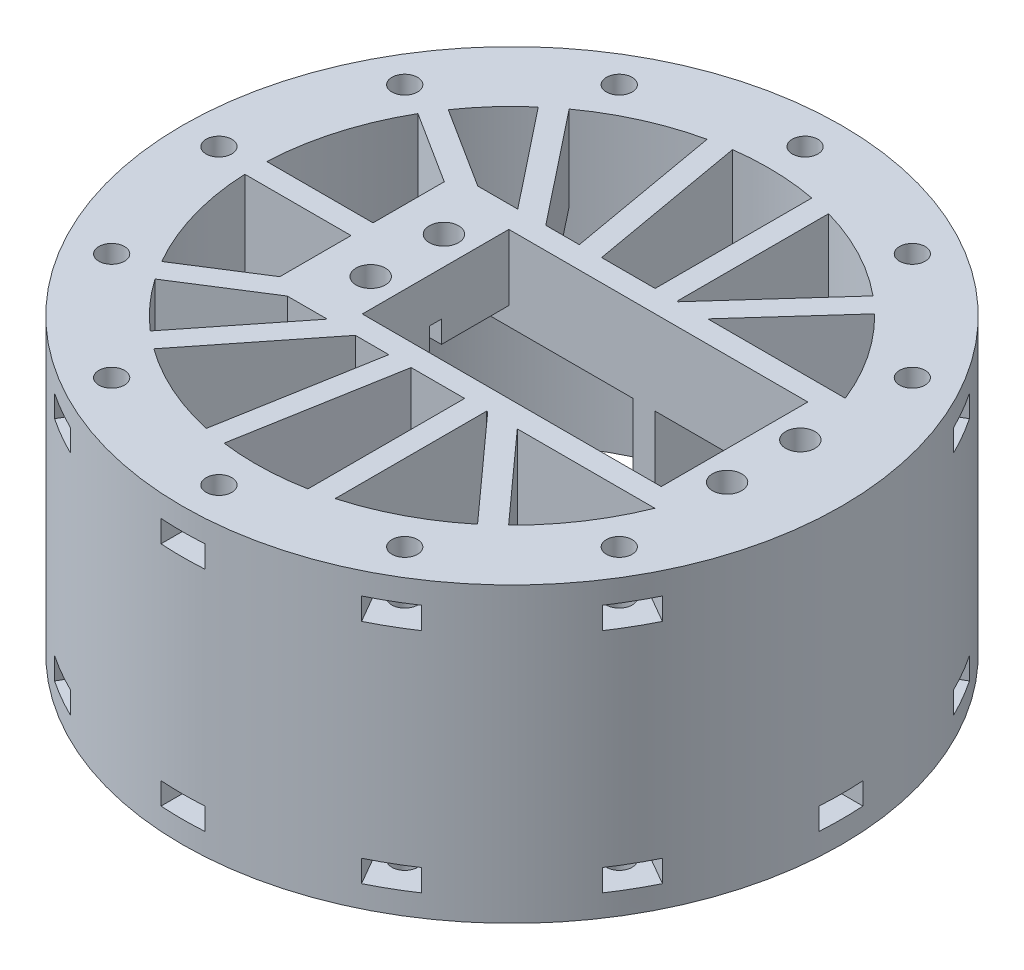
SolidWorks part; units mm, degrees
ref_plane "Front Plane" through (0, 0, 0) normal (0, 0, 1) x (1, 0, 0)
ref_plane "Top Plane" through (0, 0, 0) normal (0, 1, 0) x (1, 0, 0)
ref_plane "Right Plane" through (0, 0, 0) normal (1, 0, 0) x (0, 0, -1)
sketch "Sketch1" plane through (0, 0, 0) normal (0, 1, 0) x (1, 0, 0)
  line L0 (-43.0464, 0) -> (41.9462, 0) construction
  line L1 (0, 43.1152) -> (0, -41.8775) construction
  circle A1 centre (0, 0) radius 45
  dimension "D2" = 90
extrude "Boss-Extrude1" add sketch "Sketch1" along normal blind 40
sketch "Sketch2" plane through (0, 0, 0) normal (0, -1, 0) x (1, 0, 0)
  circle A0 centre (0, 0) radius 35
  dimension "D1" = 70
extrude "Cut-Extrude1" cut sketch "Sketch2" against normal blind 28.5
sketch "Sketch3" plane through (0, 28.5, 0) normal (0, -1, 0) x (1, 0, 0)
  line L0 (35, 0) -> (-35, 0) construction
  line L1 (0, -35) -> (0, 35) construction
  line L3 (37.5324, -10) -> (-17.4676, -10)
  line L4 (37.5324, -10) -> (37.5324, 10)
  line L5 (37.5324, 10) -> (-17.4676, 10)
  line L6 (-17.4676, -10) -> (-17.4676, 10)
  circle A0 centre (0, 0) radius 35 construction
  circle A1 centre (0, 0) radius 35 construction
  dimension "D1" = 20
  dimension "D2" = 55
  dimension "D3" = 10
  dimension "D4" = 37.5324
extrude "Cut-Extrude2" cut sketch "Sketch3" against normal blind 2.5 and the other way up to next
sketch "Sketch4" plane through (0, 31, 0) normal (0, -1, 0) x (1, 0, 0)
  line L0 (37.5324, 0) -> (-17.4676, 0) construction
  line L1 (37.5324, 10) -> (37.5324, -10) construction
  line L2 (-17.4676, 10) -> (-17.4676, -10) construction
  line L3 (0, -10) -> (0, 10) construction
  line L4 (-17.4676, -10) -> (33.541, -10) construction
  line L5 (33.541, 10) -> (-17.4676, 10) construction
  line L7 (30.3722, -10) -> (-10.4278, -10)
  line L8 (30.3722, -10) -> (30.3722, 10)
  line L9 (30.3722, 10) -> (-10.4278, 10)
  line L10 (-10.4278, -10) -> (-10.4278, 10)
  dimension "D1" = 20
  dimension "D2" = 40.8
  dimension "D3" = 30.3722
  dimension "D4" = 10
extrude "Cut-Extrude3" cut sketch "Sketch4" against normal blind 9
sketch "Sketch8" plane through (0, 28.5, 0) normal (0, -1, 0) x (1, 0, 0)
  line L0 (-17.4676, 0) -> (-35, 0) construction
  line L1 (-17.4676, 10) -> (-17.4676, -10) construction
  line L2 (8.0367, 10) -> (8.0367, 34.0648) construction
  line L3 (33.541, 10) -> (-17.4676, 10) construction
  line L4 (8.0367, -10) -> (8.0367, -29.3194) construction
  line L5 (-17.4676, -10) -> (33.541, -10) construction
  line L6 (6.5367, 10) -> (6.5367, 34.3842)
  line L7 (9.5367, 10) -> (9.5367, 33.6757)
  line L8 (9.5367, 10) -> (6.5367, 10)
  line L9 (9.5367, -10) -> (6.5367, -10)
  line L10 (6.5367, -10) -> (6.5367, -34.3842)
  line L11 (9.5367, -10) -> (9.5367, -33.6757)
  line L12 (-17.4676, 1.5) -> (-34.9678, 1.5)
  line L13 (-17.4676, -1.5) -> (-34.9678, -1.5)
  line L14 (-17.4676, 1.5) -> (-17.4676, -1.5)
  arc A0 (33.541, 10) -> (33.541, -10) centre (0, 0) ccw construction
  arc A1 (9.5367, 33.6757) -> (6.5367, 34.3842) centre (7.9531, 33.6757) ccw
  arc A2 (9.5367, -33.6757) -> (6.5367, -34.3842) centre (7.9531, -33.6757) cw
  arc A3 (-34.9678, 1.5) -> (-34.9678, -1.5) centre (-34.9678, 0) ccw
  dimension "D3" = 1.5
  dimension "D1" = 1.5
  dimension "D2" = 1.5
  dimension "D4" = 1.5
extrude "Boss-Extrude2" add sketch "Sketch8" along normal through all
sketch "Sketch16" plane through (0, 31, 0) normal (0, -1, 0) x (1, 0, 0)
  line L0 (-17.4676, 0) -> (37.5324, 0) construction
  line L1 (-17.4676, 10) -> (-17.4676, -10) construction
  line L2 (37.5324, -10) -> (37.5324, 10) construction
  line L3 (30.3722, -0.8) -> (37.5324, -0.8)
  line L4 (-10.4278, -0.8) -> (-17.4676, -0.8)
  line L5 (-10.4278, 10) -> (-10.4278, -10) construction
  line L6 (-10.4278, 0.8) -> (-17.4676, 0.8)
  line L7 (-17.4676, 0.8) -> (-17.4676, -0.8)
  line L8 (-10.4278, 0.8) -> (-10.4278, -0.8)
  line L9 (30.3722, -10) -> (30.3722, 10) construction
  line L10 (30.3722, 0.8) -> (37.5324, 0.8)
  line L11 (37.5324, 0.8) -> (37.5324, -0.8)
  line L12 (30.3722, 0.8) -> (30.3722, -0.8)
  dimension "D1" = 0.8
extrude "Cut-Extrude10" cut sketch "Sketch16" against normal blind 3
sketch "Sketch27" plane through (0, 0, 0) normal (0, -1, 0) x (1, 0, 0)
  line L0 (0, 0) -> (0, -53.17) construction
  line L1 (0, 0) -> (47.7582, -27.5732) construction
  line L3 (31.641, -18.2679) -> (31.641, -21.7321) construction
  line L4 (31.641, -21.7321) -> (34.641, -23.4641) construction
  line L5 (34.641, -23.4641) -> (37.641, -21.7321) construction
  line L6 (37.641, -21.7321) -> (37.641, -18.2679) construction
  line L7 (37.641, -18.2679) -> (34.641, -16.5359) construction
  line L8 (34.641, -16.5359) -> (31.641, -18.2679) construction
  circle A0 centre (0, 0) radius 40 construction
  circle A1 centre (34.641, -20) radius 1.75
  circle A2 centre (0, 0) radius 35 construction
  circle A3 centre (34.641, -20) radius 3 construction
  circle A4 centre (20, -34.641) radius 1.75
  circle A5 centre (0, -40) radius 1.75
  circle A6 centre (-20, -34.641) radius 1.75
  circle A7 centre (-34.641, -20) radius 1.75
  circle A8 centre (-40, 0) radius 1.75
  circle A9 centre (-34.641, 20) radius 1.75
  circle A10 centre (-20, 34.641) radius 1.75
  circle A11 centre (0, 40) radius 1.75
  circle A12 centre (20, 34.641) radius 1.75
  circle A13 centre (34.641, 20) radius 1.75
  circle A15 centre (40, 0) radius 1.75 [skipped]
  point P28 (0, 0)
  point P41 (0, 0)
  dimension "D1" = 80
  dimension "D3" = 3.5
  dimension "D4" = 70
  dimension "D5" = 6
  dimension "D6" = 12
  dimension "D2" = 60
extrude "Cut-Extrude15" cut sketch "Sketch27" against normal through all
ref_plane "Plane1" through (0, 37, 0) normal (0, 1, 0) x (1, 0, 0)
sketch "Sketch28" plane through (0, 37, 0) normal (0, 1, 0) x (1, 0, 0)
  line L0 (0, 0) -> (-54.493, 0) construction
  line L1 (-31.641, 18.2679) -> (-31.641, 21.7321)
  line L2 (-36.5359, 0) -> (-38.2679, 3)
  line L3 (-38.2679, 3) -> (-44.8999, 3)
  line L4 (-31.641, 21.7321) -> (-37.3844, 25.048)
  line L5 (-40.3844, 19.8519) -> (-34.641, 16.5359)
  line L6 (-44.8999, -3) -> (-38.2679, -3)
  line L7 (-38.2679, -3) -> (-36.5359, 0)
  line L8 (-43.4641, 0) -> (-42.5981, -1.5) [skipped]
  line L9 (-41.7321, 3) -> (-42.5981, 1.5) [skipped]
  line L10 (-34.641, 16.5359) -> (-31.641, 18.2679)
  line L11 (-18.2679, 31.641) -> (-16.5359, 34.641)
  line L12 (-16.5359, 34.641) -> (-19.8519, 40.3844)
  line L13 (-25.048, 37.3844) -> (-21.7321, 31.641)
  line L14 (-21.7321, 31.641) -> (-18.2679, 31.641)
  line L15 (0, 36.5359) -> (3, 38.2679)
  line L16 (3, 38.2679) -> (3, 44.8999)
  line L17 (-3, 44.8999) -> (-3, 38.2679)
  line L18 (-3, 38.2679) -> (0, 36.5359)
  line L19 (18.2679, 31.641) -> (21.7321, 31.641)
  line L20 (21.7321, 31.641) -> (25.048, 37.3844)
  line L21 (19.8519, 40.3844) -> (16.5359, 34.641)
  line L22 (16.5359, 34.641) -> (18.2679, 31.641)
  line L23 (31.641, 18.2679) -> (34.641, 16.5359)
  line L24 (34.641, 16.5359) -> (40.3844, 19.8519)
  line L25 (37.3844, 25.048) -> (31.641, 21.7321)
  line L26 (31.641, 21.7321) -> (31.641, 18.2679)
  line L31 (31.641, -18.2679) -> (31.641, -21.7321)
  line L32 (31.641, -21.7321) -> (37.3844, -25.048)
  line L33 (40.3844, -19.8519) -> (34.641, -16.5359)
  line L34 (34.641, -16.5359) -> (31.641, -18.2679)
  line L35 (18.2679, -31.641) -> (16.5359, -34.641)
  line L36 (16.5359, -34.641) -> (19.8519, -40.3844)
  line L37 (25.048, -37.3844) -> (21.7321, -31.641)
  line L38 (21.7321, -31.641) -> (18.2679, -31.641)
  line L39 (0, -36.5359) -> (-3, -38.2679)
  line L40 (-3, -38.2679) -> (-3, -44.8999)
  line L41 (3, -44.8999) -> (3, -38.2679)
  line L42 (3, -38.2679) -> (0, -36.5359)
  line L43 (-18.2679, -31.641) -> (-21.7321, -31.641)
  line L44 (-21.7321, -31.641) -> (-25.048, -37.3844)
  line L45 (-19.8519, -40.3844) -> (-16.5359, -34.641)
  line L46 (-16.5359, -34.641) -> (-18.2679, -31.641)
  line L47 (-31.641, -18.2679) -> (-34.641, -16.5359)
  line L48 (-34.641, -16.5359) -> (-40.3844, -19.8519)
  line L49 (-37.3844, -25.048) -> (-31.641, -21.7321)
  line L50 (-31.641, -21.7321) -> (-31.641, -18.2679)
  line L51 (36.5359, 0) -> (38.2679, -3) [skipped]
  line L52 (38.2679, -3) -> (44.8999, -3) [skipped]
  line L53 (44.8999, 3) -> (38.2679, 3) [skipped]
  line L54 (38.2679, 3) -> (36.5359, 0) [skipped]
  arc A0 (-44.8999, 3) -> (-44.8999, -3) centre (0, 0) ccw
  circle A1 centre (-40, 0) radius 3 construction
  arc A2 (-37.3844, 25.048) -> (-40.3844, 19.8519) centre (0, 0) ccw
  circle A3 centre (-34.641, 20) radius 3 construction
  arc A4 (-19.8519, 40.3844) -> (-25.048, 37.3844) centre (0, 0) ccw
  circle A5 centre (-20, 34.641) radius 3 construction
  arc A6 (3, 44.8999) -> (-3, 44.8999) centre (0, 0) ccw
  circle A7 centre (0, 40) radius 3 construction
  arc A8 (25.048, 37.3844) -> (19.8519, 40.3844) centre (0, 0) ccw
  circle A9 centre (20, 34.641) radius 3 construction
  arc A10 (40.3844, 19.8519) -> (37.3844, 25.048) centre (0, 0) ccw
  circle A11 centre (34.641, 20) radius 3 construction
  arc A14 (37.3844, -25.048) -> (40.3844, -19.8519) centre (0, 0) ccw
  circle A15 centre (34.641, -20) radius 3 construction
  arc A16 (19.8519, -40.3844) -> (25.048, -37.3844) centre (0, 0) ccw
  circle A17 centre (20, -34.641) radius 3 construction
  arc A18 (-3, -44.8999) -> (3, -44.8999) centre (0, 0) ccw
  circle A19 centre (0, -40) radius 3 construction
  arc A20 (-25.048, -37.3844) -> (-19.8519, -40.3844) centre (0, 0) ccw
  circle A21 centre (-20, -34.641) radius 3 construction
  arc A22 (-40.3844, -19.8519) -> (-37.3844, -25.048) centre (0, 0) ccw
  circle A23 centre (-34.641, -20) radius 3 construction
  arc A24 (44.8999, -3) -> (44.8999, 3) centre (0, 0) ccw [skipped]
  circle A25 centre (40, 0) radius 3 construction
  point P94 (0, 0)
  dimension "D1" = 90
  dimension "D2" = 6
  dimension "D3" = 12
extrude "Cut-Extrude17" cut sketch "Sketch28" against normal blind 3
sketch "Sketch29" plane through (0, 28.5, 0) normal (0, -1, 0) x (1, 0, 0)
  line L0 (32.4962, -13) -> (13.7255, -13)
  line L1 (9.5367, -33.6757) -> (9.5367, -10) construction
  line L2 (9.5367, -13) -> (9.5367, -33.6757)
  line L3 (9.5367, -10) -> (33.541, -10) construction
  line L4 (6.5367, -13) -> (-0.7691, -13)
  line L5 (6.5367, -10) -> (6.5367, -34.3842) construction
  line L6 (-20.4676, -11.223) -> (-20.4676, -1.5)
  line L7 (-34.9678, -1.5) -> (-17.4676, -1.5) construction
  line L8 (-20.4676, -1.5) -> (-34.9678, -1.5)
  line L9 (-17.4676, -0.8) -> (-17.4676, -10) construction
  line L10 (32.4962, 13) -> (13.7255, 13)
  line L11 (9.5367, 10) -> (9.5367, 33.6757) construction
  line L12 (9.5367, 13) -> (9.5367, 33.6757)
  line L13 (-7.5493, 34.1761) -> (-3.8154, 13)
  line L14 (6.5367, 13) -> (-0.7691, 13)
  line L15 (6.5367, 34.3842) -> (6.5367, 10) construction
  line L16 (-20.4676, 11.223) -> (-20.4676, 1.5)
  line L17 (-17.4676, 1.5) -> (-34.9678, 1.5) construction
  line L18 (-20.4676, 1.5) -> (-34.9678, 1.5)
  line L19 (6.5367, 13) -> (6.5367, 34.3842)
  line L20 (6.5367, -34.3842) -> (6.5367, -13)
  line L21 (0, 0) -> (-21.7353, -27.4331) construction
  line L22 (-20.5397, -28.3394) -> (-8.3862, -13)
  line L23 (-22.8911, -26.4764) -> (-12.2137, -13)
  line L24 (0, 0) -> (-20.4676, -13) construction
  line L25 (-17.6698, -13) -> (-28.713, -20.0141)
  line L26 (-20.4676, -11.223) -> (-30.3215, -17.4817)
  line L27 (0, 0) -> (-35, 0) construction
  line L28 (-20.4676, 11.223) -> (-30.3215, 17.4817)
  line L29 (-17.6698, 13) -> (-28.713, 20.0141)
  line L30 (-22.8911, 26.4764) -> (-12.2137, 13)
  line L31 (-20.5397, 28.3394) -> (-8.3862, 13)
  line L32 (-12.2137, 13) -> (-17.6698, 13)
  line L33 (0, 0) -> (-6.0777, -34.4683) construction
  line L34 (-4.5949, -34.6971) -> (-0.7691, -13)
  line L35 (-7.5493, -34.1761) -> (-3.8154, -13)
  line L36 (-3.8154, -13) -> (-17.6698, -13)
  line L37 (-4.5949, 34.6971) -> (-0.7691, 13)
  line L38 (-3.8154, 13) -> (-8.3862, 13)
  line L39 (0, 0) -> (23.4214, -26.0084) construction
  line L40 (9.6883, -13) -> (22.2852, -26.9883)
  line L41 (13.7255, -13) -> (24.5145, -24.9808)
  line L42 (13.7255, 13) -> (24.5145, 24.9808)
  line L43 (9.6883, 13) -> (22.2852, 26.9883)
  line L44 (9.6883, -13) -> (9.5367, -13)
  line L45 (9.6883, 13) -> (9.5367, 13)
  arc A0 (9.5367, -33.6757) -> (22.2852, -26.9883) centre (0, 0) ccw
  arc A1 (6.5367, 34.3842) -> (-4.5949, 34.6971) centre (0, 0) ccw
  arc A2 (32.4962, 13) -> (24.5145, 24.9808) centre (0, 0) ccw
  arc A3 (-34.9678, -1.5) -> (-30.3215, -17.4817) centre (0, 0) ccw
  circle A4 centre (0, 0) radius 35 construction
  arc A5 (-7.5493, 34.1761) -> (-20.5397, 28.3394) centre (0, 0) ccw
  arc A6 (-4.5949, -34.6971) -> (6.5367, -34.3842) centre (0, 0) ccw
  arc A7 (-20.5397, -28.3394) -> (-7.5493, -34.1761) centre (0, 0) ccw
  arc A8 (-28.713, -20.0141) -> (-22.8911, -26.4764) centre (0, 0) ccw
  arc A9 (-30.3215, 17.4817) -> (-34.9678, 1.5) centre (0, 0) ccw
  arc A10 (-22.8911, 26.4764) -> (-28.713, 20.0141) centre (0, 0) ccw
  arc A11 (24.5145, -24.9808) -> (32.4962, -13) centre (0, 0) ccw
  arc A12 (22.2852, 26.9883) -> (9.5367, 33.6757) centre (0, 0) ccw
  point P11 (21.5389, -10)
  point P23 (-17.4676, -5.4)
  line M3 (-17.4676, -1.5) -> (-34.9678, -1.5)
  arc M4 (-34.9678, -1.5) -> (6.5367, -34.3842) centre (0, 0) ccw
  line M5 (6.5367, -34.3842) -> (6.5367, -10)
  dimension "D1" = 1.5
  dimension "D2" = 3
  dimension "D3" = 3
  dimension "D4" = 80
  dimension "D5" = 1.5
  dimension "D6" = 1.5
  dimension "D7" = 1.5
sketch "Sketch32" plane through (0, 31, 0) normal (0, -1, 0) x (1, 0, 0)
  line L0 (-17.4676, 0) -> (37.5324, 0) construction
  line L1 (-17.4676, -1.5) -> (-17.4676, 1.5) construction
  line L2 (37.5324, 10) -> (37.5324, -10) construction
  line L3 (10.0324, 0) -> (10.0324, -10) construction
  line L6 (9.5367, -10) -> (33.541, -10) construction
  circle A0 centre (-14.2876, -5) radius 2
  circle A1 centre (-14.2876, 5) radius 2
  circle A2 centre (34.3524, -5) radius 2
  circle A3 centre (34.3524, 5) radius 2
  dimension "D1" = 24.32
  dimension "D3" = 4
  dimension "D2" = 5
extrude "Cut-Extrude21" cut sketch "Sketch32" against normal through all
extrude "Cut-Extrude22" cut sketch "Sketch29" against normal blind 12 contours L28 A9 L18 L16 | L26 L6 M3 M4 | L23 L36 L25 M4 | L35 L36 L22 M4 | L34 L4 M4 M5 | L2 A0 L40 L44 | L41 A11 L0 | L10 A2 L42 | L43 A12 L12 L45 | L19 A1 L37 L14 | L13 A5 L31 L38 | L30 A10 L29 L32 region at (23.89, 28.5, -17.1237) region at (13.9029, 28.5, -24.813) region at (1.8383, 28.5, -24.6789) region at (-27.5459, 28.5, -7.8919) region at (-10.8152, 28.5, -24.1049) region at (-20.9968, 28.5, -18.9781) region at (23.89, 28.5, 17.1237) region at (13.9029, 28.5, 24.813) region at (-10.8152, 28.5, 24.1049) region at (1.8383, 28.5, 24.6789) region at (-27.5459, 28.5, 7.8919) region at (-20.9968, 28.5, 18.9781)
sketch "Sketch33" plane through (0, 0, 1.5) normal (0, 0, 1) x (1, 0, 0)
  line L0 (-17.4676, 14.25) -> (-34.9678, 0)
  line L1 (-17.4676, 0) -> (-17.4676, 28.5) construction
  line L2 (-34.9678, 0) -> (-17.4676, 0)
  line L3 (-17.4676, 0) -> (-34.9678, 0) construction
  line L4 (-17.4676, 0) -> (-17.4676, 14.25)
extrude "Cut-Extrude23" cut sketch "Sketch33" against normal up to next
ref_plane "Plane2" through (0, 3, 0) normal (0, -1, 0) x (-1, 0, 0)
sketch "Sketch34" plane through (0, 3, 0) normal (0, -1, 0) x (-1, 0, 0)
  line L0 (0, 0) -> (0, 45) construction
  line L1 (18.2679, 31.641) -> (21.7321, 31.641)
  line L2 (0, 36.5359) -> (3, 38.2679)
  line L3 (3, 38.2679) -> (3, 44.8999)
  line L4 (21.7321, 31.641) -> (25.048, 37.3844)
  line L5 (19.8519, 40.3844) -> (16.5359, 34.641)
  line L6 (-3, 44.8999) -> (-3, 38.2679)
  line L7 (-3, 38.2679) -> (0, 36.5359)
  line L8 (0, 43.4641) -> (-1.5, 42.5981) [skipped]
  line L9 (3, 41.7321) -> (1.5, 42.5981) [skipped]
  line L10 (16.5359, 34.641) -> (18.2679, 31.641)
  line L11 (31.641, 18.2679) -> (34.641, 16.5359)
  line L12 (34.641, 16.5359) -> (40.3844, 19.8519)
  line L13 (37.3844, 25.048) -> (31.641, 21.7321)
  line L14 (31.641, 21.7321) -> (31.641, 18.2679)
  line L15 (36.5359, 0) -> (38.2679, -3)
  line L16 (38.2679, -3) -> (44.8999, -3)
  line L17 (44.8999, 3) -> (38.2679, 3)
  line L18 (38.2679, 3) -> (36.5359, 0)
  line L19 (31.641, -18.2679) -> (31.641, -21.7321)
  line L20 (31.641, -21.7321) -> (37.3844, -25.048)
  line L21 (40.3844, -19.8519) -> (34.641, -16.5359)
  line L22 (34.641, -16.5359) -> (31.641, -18.2679)
  line L23 (18.2679, -31.641) -> (16.5359, -34.641)
  line L24 (16.5359, -34.641) -> (19.8519, -40.3844)
  line L25 (25.048, -37.3844) -> (21.7321, -31.641)
  line L26 (21.7321, -31.641) -> (18.2679, -31.641)
  line L27 (0, -36.5359) -> (-3, -38.2679)
  line L28 (-3, -38.2679) -> (-3, -44.8999)
  line L29 (3, -44.8999) -> (3, -38.2679)
  line L30 (3, -38.2679) -> (0, -36.5359)
  line L31 (-18.2679, -31.641) -> (-21.7321, -31.641)
  line L32 (-21.7321, -31.641) -> (-25.048, -37.3844)
  line L33 (-19.8519, -40.3844) -> (-16.5359, -34.641)
  line L34 (-16.5359, -34.641) -> (-18.2679, -31.641)
  line L35 (-31.641, -18.2679) -> (-34.641, -16.5359)
  line L36 (-34.641, -16.5359) -> (-40.3844, -19.8519)
  line L37 (-37.3844, -25.048) -> (-31.641, -21.7321)
  line L38 (-31.641, -21.7321) -> (-31.641, -18.2679)
  line L39 (-36.5359, 0) -> (-38.2679, 3)
  line L40 (-38.2679, 3) -> (-44.8999, 3)
  line L41 (-44.8999, -3) -> (-38.2679, -3)
  line L42 (-38.2679, -3) -> (-36.5359, 0)
  line L43 (-31.641, 18.2679) -> (-31.641, 21.7321)
  line L44 (-31.641, 21.7321) -> (-37.3844, 25.048)
  line L45 (-40.3844, 19.8519) -> (-34.641, 16.5359)
  line L46 (-34.641, 16.5359) -> (-31.641, 18.2679)
  line L47 (-18.2679, 31.641) -> (-16.5359, 34.641)
  line L48 (-16.5359, 34.641) -> (-19.8519, 40.3844)
  line L49 (-25.048, 37.3844) -> (-21.7321, 31.641)
  line L50 (-21.7321, 31.641) -> (-18.2679, 31.641)
  circle A0 centre (0, 0) radius 45 construction
  circle A1 centre (0, 40) radius 3 construction
  arc A2 (3, 44.8999) -> (-3, 44.8999) centre (0, 0) ccw
  arc A3 (25.048, 37.3844) -> (19.8519, 40.3844) centre (0, 0) ccw
  circle A4 centre (20, 34.641) radius 3 construction
  arc A5 (40.3844, 19.8519) -> (37.3844, 25.048) centre (0, 0) ccw
  circle A6 centre (34.641, 20) radius 3 construction
  arc A7 (44.8999, -3) -> (44.8999, 3) centre (0, 0) ccw
  circle A8 centre (40, 0) radius 3 construction
  arc A9 (37.3844, -25.048) -> (40.3844, -19.8519) centre (0, 0) ccw
  circle A10 centre (34.641, -20) radius 3 construction
  arc A11 (19.8519, -40.3844) -> (25.048, -37.3844) centre (0, 0) ccw
  circle A12 centre (20, -34.641) radius 3 construction
  arc A13 (-3, -44.8999) -> (3, -44.8999) centre (0, 0) ccw
  circle A14 centre (0, -40) radius 3 construction
  arc A15 (-25.048, -37.3844) -> (-19.8519, -40.3844) centre (0, 0) ccw
  circle A16 centre (-20, -34.641) radius 3 construction
  arc A17 (-40.3844, -19.8519) -> (-37.3844, -25.048) centre (0, 0) ccw
  circle A18 centre (-34.641, -20) radius 3 construction
  arc A19 (-44.8999, 3) -> (-44.8999, -3) centre (0, 0) ccw
  circle A20 centre (-40, 0) radius 3 construction
  arc A21 (-37.3844, 25.048) -> (-40.3844, 19.8519) centre (0, 0) ccw
  circle A22 centre (-34.641, 20) radius 3 construction
  arc A23 (-19.8519, 40.3844) -> (-25.048, 37.3844) centre (0, 0) ccw
  circle A24 centre (-20, 34.641) radius 3 construction
  point P98 (0, 0)
  dimension "D1" = 6
  dimension "D2" = 90
  dimension "D3" = 12
extrude "Cut-Extrude24" cut sketch "Sketch34" against normal blind 3
